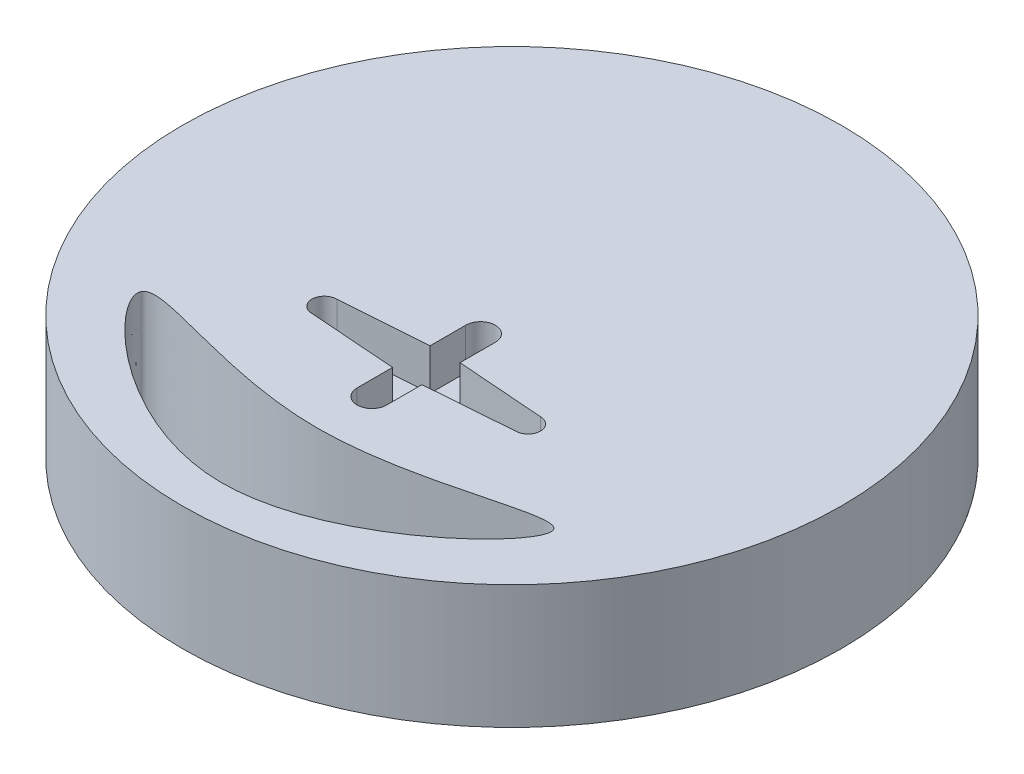
SolidWorks part; units mm, degrees
ref_plane "Front Plane" through (0, 0, 0) normal (0, 0, 1) x (1, 0, 0)
ref_plane "Top Plane" through (0, 0, 0) normal (0, 1, 0) x (1, 0, 0)
ref_plane "Right Plane" through (0, 0, 0) normal (1, 0, 0) x (0, 0, -1)
sketch "Sketch1" plane through (0, 0, 0) normal (0, 1, 0) x (1, 0, 0)
  circle A0 centre (0, 0) radius 50.8
extrude "Boss-Extrude1" add sketch "Sketch1" along normal blind 19.05
sketch "Sketch2" plane through (0, 19.05, 0) normal (0, 1, 0) x (1, 0, 0)
  line L0 (0, 10.8607) -> (0, -26.0542) construction
  line L1 (-15.6972, -13.2075) -> (15.6972, -13.2075) construction
  line L2 (-15.6972, -11.2903) -> (-2.2819, -10.3199)
  line L3 (2.2819, -10.2735) -> (15.6972, -11.2903)
  line L4 (-15.6972, -15.1247) -> (-2.2819, -16.0951)
  line L5 (2.2819, -16.1415) -> (15.6972, -15.1247)
  line L6 (-2.2819, -16.0951) -> (-2.2819, -21.5844)
  line L7 (-2.2819, -4.8306) -> (-2.2819, -10.3199)
  line L8 (2.2819, -4.8306) -> (2.2819, -10.2735)
  line L9 (2.2819, -16.1415) -> (2.2819, -21.5844)
  line L10 (0, -4.8306) -> (0, -21.5844) construction
  arc A1 (-15.6972, -11.2903) -> (-15.6972, -15.1247) centre (-15.6972, -13.2075) ccw
  arc A2 (15.6972, -15.1247) -> (15.6972, -11.2903) centre (15.6972, -13.2075) ccw
  circle A3 centre (0, 0) radius 50.8 construction
  arc A4 (2.2819, -4.8306) -> (-2.2819, -4.8306) centre (0, -4.8306) ccw
  arc A5 (-2.2819, -21.5844) -> (2.2819, -21.5844) centre (0, -21.5844) ccw
  point P3 (0, -13.2075)
  dimension "D1" = 15.6972
extrude "Cut-Extrude1" cut sketch "Sketch2" against normal blind 6.35
sketch "Sketch3" plane through (0, 19.05, 0) normal (0, 1, 0) x (1, 0, 0)
  line L0 (0, 12.8335) -> (0, -72.8433) construction
  spline S0 degree 3 poles (0, -37.2991) (-47.8547, -14.2596) (0, -61.0011) (47.8547, -14.2596) (0, -37.2991) (-47.8547, -14.2596) (0, -61.0011) knots -0.731633 -0.463265 -0.231633 0 0.268367 0.536735 0.768367 1 1.268367 1.536735 1.768367 only from (-31.75, -25.3233) to (-31.75, -25.3233)
  point P5 (-31.5066, -25.3233)
  dimension "D1" = 63.5
  dimension "D2" = 31.75
  dimension "D3" = 0
extrude "Cut-Extrude2" cut sketch "Sketch3" against normal through all
sketch "Sketch4" plane through (0, 0, 0) normal (0, -1, 0) x (1, 0, 0)
  line L0 (-44.4379, -24.6153) -> (-25.3879, -24.6153)
  line L1 (25.3879, -24.6153) -> (44.4379, -24.6153)
  line L3 (-25.3879, 1.7897) -> (25.3879, 1.7897)
  line L4 (-25.3879, 1.7897) -> (-25.3879, -24.6153)
  line L6 (25.3879, 1.7897) -> (25.3879, -24.6153)
  line L7 (-25.3879, 1.7897) -> (25.3879, -24.6153) construction
  line L8 (-25.3879, -24.6153) -> (25.3879, 1.7897) construction
  circle A0 centre (0, 0) radius 50.8 construction
  arc A1 (-44.4379, -24.6153) -> (44.4379, -24.6153) centre (0, 0) ccw
  point P5 (0, -11.4128)
  dimension "D1" = 19.05
  dimension "D2" = 19.05
extrude "Boss-Extrude2" add sketch "Sketch4" along normal blind 19.05 draft 25 separate body
sketch "Sketch6" plane through (0, 0, 0) normal (0, 0, 1) x (1, 0, 0)
  circle A0 centre (0, -10.16) radius 7.62
  dimension "D1" = 10.16
  dimension "D2" = 15.24
extrude "Cut-Extrude3" cut sketch "Sketch6" against normal through all
